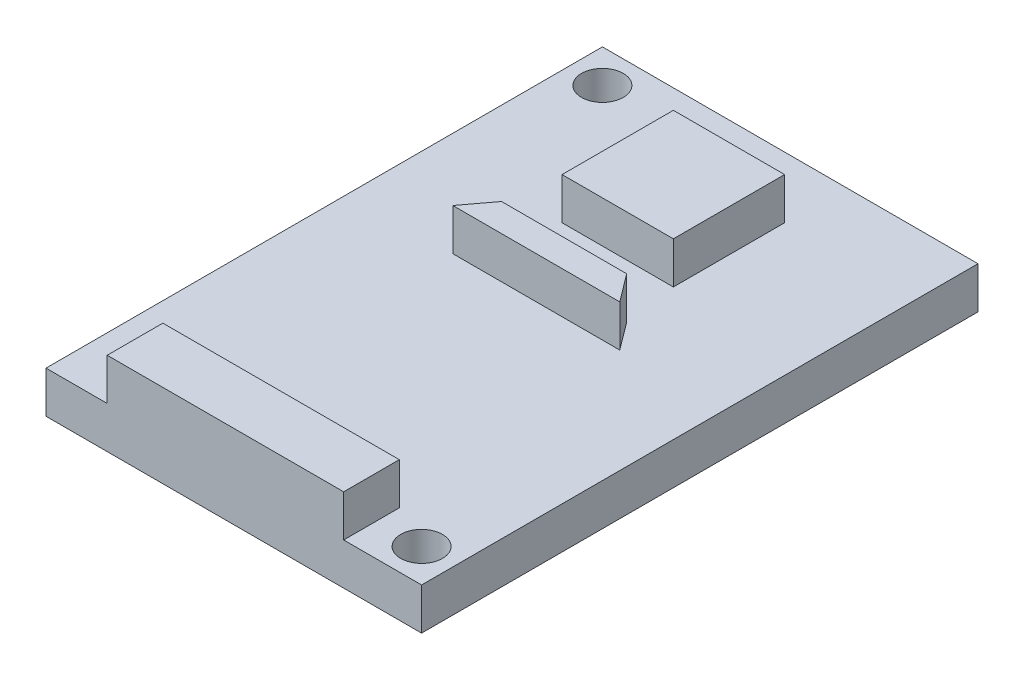
SolidWorks part; units mm, degrees
ref_plane "Front Plane" through (0, 0, 0) normal (0, 0, 1) x (1, 0, 0)
ref_plane "Top Plane" through (0, 0, 0) normal (0, 1, 0) x (1, 0, 0)
ref_plane "Right Plane" through (0, 0, 0) normal (1, 0, 0) x (0, 0, -1)
sketch "Sketch1" plane through (0, 0, 0) normal (0, 1, 0) x (1, 0, 0)
  line L1 (0, 0) -> (13.5, 0)
  line L2 (0, 0) -> (0, 20)
  line L3 (0, 20) -> (13.5, 20)
  line L4 (13.5, 0) -> (13.5, 20)
  dimension "D1" = 20
  dimension "D2" = 13.5
extrude "Boss-Extrude1" add sketch "Sketch1" along normal blind 1.5
sketch "Sketch2" plane through (0, 1.5, 0) normal (0, 1, 0) x (1, 0, 0)
  line L0 (13.5, 20) -> (0, 20) construction
  line L1 (4.75, 17.8) -> (8.75, 17.8)
  line L2 (4.75, 17.8) -> (4.75, 13.8)
  line L3 (4.75, 13.8) -> (8.75, 13.8)
  line L4 (8.75, 17.8) -> (8.75, 13.8)
  line L5 (0, 20) -> (0, 0) construction
  line L7 (13.5, 0) -> (13.5, 20) construction
  line L8 (4.5, 11.8732) -> (9, 11.8732)
  line L9 (3.75, 10.8732) -> (9.75, 10.8732)
  line L10 (4.5, 11.8732) -> (3.75, 10.8732)
  line L11 (9, 11.8732) -> (9.75, 10.8732)
  dimension "D1" = 4
  dimension "D2" = 4
  dimension "D3" = 2.2
  dimension "D4" = 4.75
  dimension "D5" = 4.75
  dimension "D6" = 1
  dimension "D7" = 4.5
  dimension "D8" = 4.5
  dimension "D9" = 3.75
  dimension "D10" = 3.75
extrude "Boss-Extrude2" add sketch "Sketch2" along normal blind 1.5
sketch "Sketch3" plane through (0, 0, 0) normal (0, -1, 0) x (1, 0, 0)
  line L0 (0, -20) -> (0, 0) construction
  line L1 (13.5, -20) -> (0, -20) construction
  line L2 (13.5, 0) -> (13.5, -20) construction
  line L3 (0, 0) -> (13.5, 0) construction
  circle A0 centre (1.2, -18.8) radius 0.75
  circle A1 centre (12.3, -1.2) radius 0.75
  dimension "D1" = 1.5
  dimension "D2" = 1.5
  dimension "D3" = 1.2
  dimension "D4" = 1.2
  dimension "D5" = 1.2
  dimension "D6" = 1.2
extrude "Cut-Extrude1" cut sketch "Sketch3" against normal blind 1.5
sketch "Sketch4" plane through (0, 1.5, 0) normal (0, 1, 0) x (1, 0, 0)
  line L0 (0, 0) -> (13.5, 0) construction
  line L1 (2.2, 0) -> (10.7, 0)
  line L2 (2.2, 0) -> (2.2, 2)
  line L3 (2.2, 2) -> (10.7, 2)
  line L4 (10.7, 0) -> (10.7, 2)
  line L5 (13.5, 0) -> (13.5, 20) construction
  line L6 (0, 20) -> (0, 0) construction
  dimension "D1" = 2.8
  dimension "D2" = 2.2
  dimension "D3" = 2
extrude "Boss-Extrude3" add sketch "Sketch4" along normal blind 1.5
